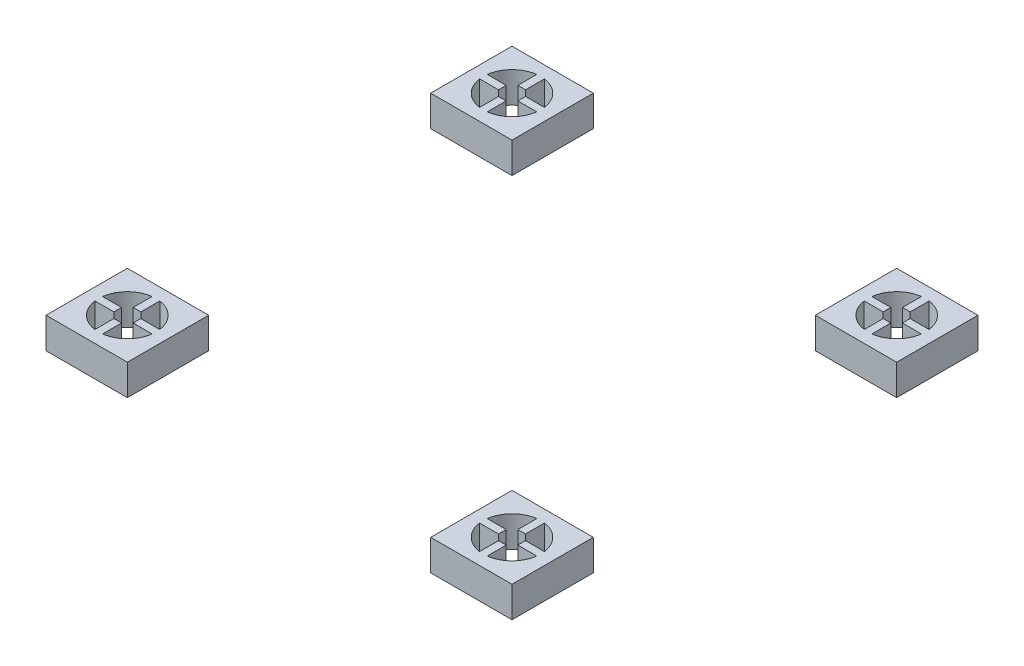
SolidWorks part; units mm, degrees
ref_plane "Front Plane" through (0, 0, 0) normal (0, 0, 1) x (1, 0, 0)
ref_plane "Top Plane" through (0, 0, 0) normal (0, 1, 0) x (1, 0, 0)
ref_plane "Right Plane" through (0, 0, 0) normal (1, 0, 0) x (0, 0, -1)
sketch "Sketch2" plane through (0, 0, 0) normal (0, 1, 0) x (1, 0, 0)
  line L0 (490, -425.6697) -> (490, -475)
  line L1 (490, -475) -> (510, -475)
  line L2 (-510, -425.6697) -> (-510, -475)
  line L3 (510, -425.6697) -> (510, -475)
  line L4 (574.3303, -510) -> (525, -510)
  line L5 (574.3303, -490) -> (525, -490)
  line L6 (525, -490) -> (525, -510)
  line L7 (490, -574.3303) -> (490, -525)
  line L8 (510, -574.3303) -> (510, -525)
  line L9 (510, -525) -> (490, -525)
  line L10 (425.6697, -490) -> (475, -490)
  line L11 (425.6697, -510) -> (475, -510)
  line L12 (475, -510) -> (475, -490)
  line L13 (500, -425) -> (500, -475) construction
  line L14 (490, 574.3303) -> (490, 525)
  line L15 (490, 525) -> (510, 525)
  line L16 (510, 574.3303) -> (510, 525)
  line L17 (574.3303, 490) -> (525, 490)
  line L18 (574.3303, 510) -> (525, 510)
  line L19 (525, 510) -> (525, 490)
  line L20 (490, 425.6697) -> (490, 475)
  line L21 (510, 425.6697) -> (510, 475)
  line L22 (510, 475) -> (490, 475)
  line L23 (425.6697, 510) -> (475, 510)
  line L24 (425.6697, 490) -> (475, 490)
  line L25 (475, 490) -> (475, 510)
  line L26 (500, 575) -> (500, 525) construction
  line L27 (-510, -475) -> (-490, -475)
  line L28 (-490, -425.6697) -> (-490, -475)
  line L29 (-425.6697, -510) -> (-475, -510)
  line L30 (-425.6697, -490) -> (-475, -490)
  line L31 (-475, -490) -> (-475, -510)
  line L32 (-510, -574.3303) -> (-510, -525)
  line L33 (-490, -574.3303) -> (-490, -525)
  line L34 (-490, -525) -> (-510, -525)
  line L35 (-574.3303, -490) -> (-525, -490)
  line L36 (-574.3303, -510) -> (-525, -510)
  line L37 (-525, -510) -> (-525, -490)
  line L38 (-510, 574.3303) -> (-510, 525)
  line L39 (-510, 525) -> (-490, 525)
  line L40 (-490, 574.3303) -> (-490, 525)
  line L41 (-425.6697, 490) -> (-475, 490)
  line L42 (-425.6697, 510) -> (-475, 510)
  line L43 (-475, 510) -> (-475, 490)
  line L44 (-510, 425.6697) -> (-510, 475)
  line L45 (-490, 425.6697) -> (-490, 475)
  line L46 (-490, 475) -> (-510, 475)
  line L47 (-574.3303, 510) -> (-525, 510)
  line L48 (-574.3303, 490) -> (-525, 490)
  line L49 (-525, 490) -> (-525, 510)
  line L50 (-500, -425) -> (-500, -475) construction
  line L51 (-500, 575) -> (-500, 525) construction
  line L52 (-605.7125, 605.7125) -> (-394.2875, 605.7125)
  line L53 (-605.7125, 605.7125) -> (-605.7125, 394.2875)
  line L54 (-605.7125, 394.2875) -> (-394.2875, 394.2875)
  line L55 (-394.2875, 605.7125) -> (-394.2875, 394.2875)
  line L56 (-605.7125, 605.7125) -> (-394.2875, 394.2875) construction
  line L57 (-605.7125, 394.2875) -> (-394.2875, 605.7125) construction
  line L58 (-605.7125, -394.2875) -> (-394.2875, -394.2875)
  line L59 (-605.7125, -394.2875) -> (-605.7125, -605.7125)
  line L60 (-605.7125, -605.7125) -> (-394.2875, -605.7125)
  line L61 (-394.2875, -394.2875) -> (-394.2875, -605.7125)
  line L62 (-605.7125, -394.2875) -> (-394.2875, -605.7125) construction
  line L63 (-605.7125, -605.7125) -> (-394.2875, -394.2875) construction
  line L64 (605.7125, 605.7125) -> (394.2875, 605.7125)
  line L65 (605.7125, 605.7125) -> (605.7125, 394.2875)
  line L66 (605.7125, 394.2875) -> (394.2875, 394.2875)
  line L67 (394.2875, 605.7125) -> (394.2875, 394.2875)
  line L68 (605.7125, 605.7125) -> (394.2875, 394.2875) construction
  line L69 (605.7125, 394.2875) -> (394.2875, 605.7125) construction
  line L70 (605.7125, -394.2875) -> (394.2875, -394.2875)
  line L71 (605.7125, -394.2875) -> (605.7125, -605.7125)
  line L72 (605.7125, -605.7125) -> (394.2875, -605.7125)
  line L73 (394.2875, -394.2875) -> (394.2875, -605.7125)
  line L74 (605.7125, -394.2875) -> (394.2875, -605.7125) construction
  line L75 (605.7125, -605.7125) -> (394.2875, -394.2875) construction
  arc A0 (490, -425.6697) -> (425.6697, -490) centre (500, -500) ccw
  arc A1 (425.6697, -510) -> (490, -574.3303) centre (500, -500) ccw
  arc A2 (510, -574.3303) -> (574.3303, -510) centre (500, -500) ccw
  arc A3 (574.3303, -490) -> (510, -425.6697) centre (500, -500) ccw
  arc A4 (490, -425.6697) -> (529.2889, -430.9554) centre (500, -500) cw
  arc A5 (490, 574.3303) -> (425.6697, 510) centre (500, 500) ccw
  arc A6 (425.6697, 490) -> (490, 425.6697) centre (500, 500) ccw
  arc A7 (510, 425.6697) -> (574.3303, 490) centre (500, 500) ccw
  arc A8 (574.3303, 510) -> (510, 574.3303) centre (500, 500) ccw
  arc A9 (490, 574.3303) -> (529.2889, 569.0446) centre (500, 500) cw
  arc A10 (-510, -425.6697) -> (-574.3303, -490) centre (-500, -500) ccw
  arc A11 (-574.3303, -510) -> (-510, -574.3303) centre (-500, -500) ccw
  arc A12 (-490, -574.3303) -> (-425.6697, -510) centre (-500, -500) ccw
  arc A13 (-425.6697, -490) -> (-490, -425.6697) centre (-500, -500) ccw
  arc A14 (-510, -425.6697) -> (-470.7111, -430.9554) centre (-500, -500) cw
  arc A15 (-510, 574.3303) -> (-574.3303, 510) centre (-500, 500) ccw
  arc A16 (-574.3303, 490) -> (-510, 425.6697) centre (-500, 500) ccw
  arc A17 (-490, 425.6697) -> (-425.6697, 490) centre (-500, 500) ccw
  arc A18 (-425.6697, 510) -> (-490, 574.3303) centre (-500, 500) ccw
  arc A19 (-510, 574.3303) -> (-470.7111, 569.0446) centre (-500, 500) cw
  point P22 (-500, -500)
  point P24 (-500, -500)
  point P48 (500, -500)
  point P49 (500, -500)
  point P71 (500, 500)
  point P72 (500, 500)
  point P87 (-500, 500)
  point P88 (-500, 500)
  point P104 (0, 0)
extrude "Boss-Extrude1" add sketch "Sketch2" along normal blind 80 contours L55 L52 L53 L54 A15 A19 A18 L42 L43 L41 A17 L45 L46 L44 A16 L48 L49 L47 | L64 L67 L66 L65 A5 A9 A8 L18 L19 L17 A7 L21 L22 L20 A6 L24 L25 L23 | L70 L73 L72 L71 A0 A4 A3 L5 L6 L4 A2 L8 L9 L7 A1 L11 L12 L10 | L61 L58 L59 L60 A10 A14 A13 L30 L31 L29 A12 L33 L34 L32 A11 L36 L37 L35 | A14 L2 L27 L28 | A4 L0 L1 L3 | A9 L14 L15 L16 | A19 L38 L39 L40 region at (500, 0, 450.111) region at (-500, 0, 450.111) region at (500, 0, -549.889) region at (-500, 0, -549.889) region at (-500, 0, -602.7225) region at (-500, 0, 397.2775) region at (602.7225, 0, -500) region at (602.7225, 0, 500)
